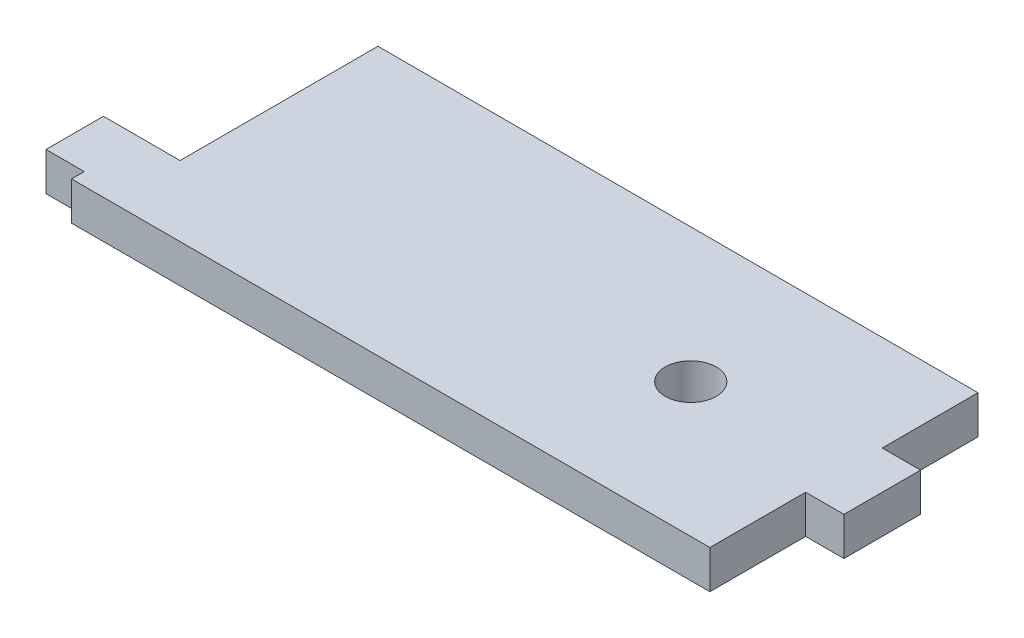
SolidWorks part; units mm, degrees
ref_plane "Front Plane" through (0, 0, 0) normal (0, 0, 1) x (1, 0, 0)
ref_plane "Top Plane" through (0, 0, 0) normal (0, 1, 0) x (1, 0, 0)
ref_plane "Right Plane" through (0, 0, 0) normal (1, 0, 0) x (0, 0, -1)
sketch "Sketch1" plane through (0, 0, 0) normal (0, 1, 0) x (1, 0, 0)
  line L1 (-47, 21) -> (47, 21)
  line L2 (-47, 21) -> (-47, -21)
  line L3 (-47, -21) -> (47, -21)
  line L4 (47, 21) -> (47, -21)
  line L5 (-47, 21) -> (47, -21) construction
  line L6 (-47, -21) -> (47, 21) construction
  point P0 (0, 0)
  dimension "D1" = 94
  dimension "D2" = 42
sketch "Sketch2" plane through (0, 0, 0) normal (0, 0, 1) x (1, 0, 0)
  line L0 (0, 0) -> (0, 6) construction
  line L1 (-47, 0) -> (47, 0) construction
  dimension "D1" = 6
extrude "Boss-Extrude1" add sketch "Sketch1" along normal up to vertex (6 mm away) contours L2 L3 L4 L1 up to point (0, 6, 0)
sketch "Sketch3" plane through (0, 0, 0) normal (0, -1, 0) x (1, 0, 0)
  line L0 (23, 0) -> (47, 0)
  line L1 (47, -21) -> (47, 21) construction
  circle A0 centre (23, 0) radius 4
  dimension "D1" = 8
  dimension "D2" = 24
extrude "Cut-Extrude1" cut sketch "Sketch3" against normal through all contours A0 region at (19.1131, 0, 0)
sketch "Sketch4" plane through (0, 6, 0) normal (0, 1, 0) x (1, 0, 0)
  line L0 (47, 21) -> (47, -21) construction
  line L1 (47, 6) -> (53, 6)
  line L2 (47, 6) -> (47, -6)
  line L3 (47, -6) -> (53, -6)
  line L4 (53, 6) -> (53, -6)
  line L5 (0, 0) -> (53, 0) construction
  point P9 (0, 0)
  dimension "D1" = 6
  dimension "D2" = 12
extrude "Boss-Extrude2" add sketch "Sketch4" against normal up to surface (6 mm away) up to face at (23, 0, -4)
sketch "Sketch5" plane through (0, 6, 0) normal (0, 1, 0) x (1, 0, 0)
  line L0 (0, 0) -> (-47, 0)
  line L1 (-47, 21) -> (-47, -21) construction
  line L2 (-47, 0) -> (-47, -10)
  line L3 (-47, -10) -> (-59, -10)
  line L4 (-59, -10) -> (-59, -19)
  line L5 (-59, -19) -> (-53, -19)
  line L6 (-53, -19) -> (-53, -21)
  line L7 (-53, -21) -> (-47, -21)
  line L8 (-47, -21) -> (-47, -10)
  line M9 (-47, 21) -> (-47, -21)
extrude "Boss-Extrude3" add sketch "Sketch5" against normal up to surface (6 mm away) contours L6 L7 L3 L4 L5 M9 region at (-52.7, 6, 15.05) up to face at (23, 0, -4)
sketch "Sketch6" plane through (0, 6, 0) normal (0, 1, 0) x (1, 0, 0)
  line L0 (23, -5) -> (23, 5) construction
  line L1 (19, -5) -> (19, 5)
  line L2 (27, -5) -> (27, 5)
  circle A0 centre (23, 0) radius 4 construction
  circle A1 centre (23, 0) radius 4
  arc A2 (19, -5) -> (27, -5) centre (23, -5) ccw
  arc A3 (27, 5) -> (19, 5) centre (23, 5) ccw
  point P5 (23, 0)
  dimension "D1" = 10
equation "\"glass_width\"= 150"
equation "\"glass_height\"= 100"
equation "\"glass_thickness\"= 4"
equation "\"brood_space\"= 42"
equation "\"t1\"= 6"
equation "\"t2\"= 6"
equation "\"box_depth\"= \"brood_space\" + \"glass_thickness\" + \"glass_thickness\" + \"t2\" + \"t2\""
equation "\"box_width\"= \"glass_width\" + \"t1\" + \"t1\""
equation "\"food_height\"= 70"
equation "\"box_height\"= \"glass_height\" + ( \"t1\" * 3 ) + \"food_height\""
equation "\"D1@Sketch1\"=\"glass_height\" - \"t1\""
equation "\"D2@Sketch1\"=\"brood_space\""
equation "\"entry_height\"= 24"
equation "\"entry_diameter\"= 8"
equation "\"food_top_clearance\"= 10"
equation "\"bar_width\"= 20"
equation "\"glassblocker_lower_height\"= 10"
equation "\"D1@Sketch3\"=\"entry_diameter\""
equation "\"D2@Sketch3\"=\"entry_height\""
equation "\"D1@Sketch2\"=\"t2\""
equation "\"D1@Sketch4\"=\"t1\""
